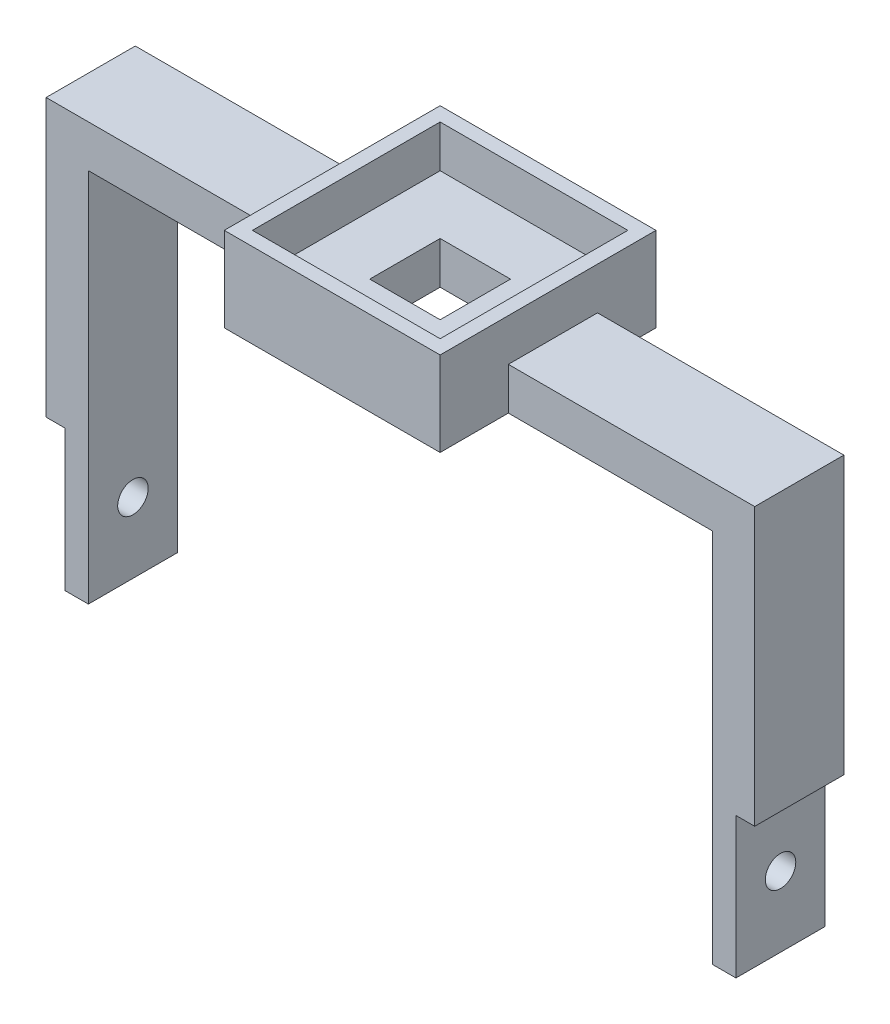
SolidWorks part; units mm, degrees
ref_plane "Ön Düzlem" through (0, 0, 0) normal (0, 0, 1) x (1, 0, 0)
ref_plane "Üst Düzlem" through (0, 0, 0) normal (0, 1, 0) x (1, 0, 0)
ref_plane "Sağ Düzlem" through (0, 0, 0) normal (1, 0, 0) x (0, 0, -1)
sketch "Çizim1" plane through (0, 0, 0) normal (0, 0, 1) x (1, 0, 0)
  line L0 (0, 0) -> (0, 80)
  line L1 (0, 80) -> (133, 80)
  line L2 (133, 80) -> (133, 0)
  line L3 (0, 0) -> (-5, 0)
  line L4 (-5, 0) -> (-5, 30)
  line L5 (142, 89) -> (-9, 89)
  line L6 (-5, 30) -> (-9, 30)
  line L7 (-9, 30) -> (-9, 89)
  line L8 (133, 0) -> (138, 0)
  line L9 (138, 0) -> (138, 30)
  line L10 (138, 30) -> (142, 30)
  line L11 (142, 30) -> (142, 89)
  dimension "D1" = 5
  dimension "D2" = 5
  dimension "D3" = 4
  dimension "D4" = 4
  dimension "D5" = 30
  dimension "D6" = 30
  dimension "D7" = 80
  dimension "D8" = 59
  dimension "D9" = 133
extrude "Yükseklik-Ekstrüzyon1" add sketch "Çizim1" along normal blind 19
sketch "Çizim2" plane through (0, 89, 0) normal (0, 1, 0) x (1, 0, 0)
  line L0 (142, 0) -> (-9, 0) construction
  line L1 (46.5, -30.5382) -> (86.5, -30.5382)
  line L2 (46.5, -30.5382) -> (46.5, 9.4618)
  line L3 (46.5, 9.4618) -> (86.5, 9.4618)
  line L4 (86.5, -30.5382) -> (86.5, 9.4618)
  line L5 (46.5, -30.5382) -> (86.5, 9.4618) construction
  line L6 (46.5, 9.4618) -> (86.5, -30.5382) construction
  point P0 (66.5, -10.5382)
  point P10 (66.5, 0)
  dimension "D1" = 40
  dimension "D2" = 40
  dimension "D3" = 0
extrude "Yükseklik-Ekstrüzyon2" add sketch "Çizim2" against normal up to surface (9 mm away) up to face at (66.5, 80, 9.5)
sketch "Çizim5" plane through (0, 89, 0) normal (0, 1, 0) x (1, 0, 0)
  line L1 (86.5, -30.5382) -> (46.5, -30.5382)
  line L2 (86.5, -30.5382) -> (86.5, 9.4618)
  line L3 (86.5, 9.4618) -> (46.5, 9.4618)
  line L4 (46.5, -30.5382) -> (46.5, 9.4618)
  line L5 (86.5, -30.5382) -> (46.5, 9.4618) construction
  line L6 (86.5, 9.4618) -> (46.5, -30.5382) construction
  line L7 (89.5, -33.5382) -> (43.5, -33.5382)
  line L8 (89.5, -33.5382) -> (89.5, 12.4618)
  line L9 (89.5, 12.4618) -> (43.5, 12.4618)
  line L10 (43.5, -33.5382) -> (43.5, 12.4618)
  line L11 (89.5, -33.5382) -> (43.5, 12.4618) construction
  line L12 (89.5, 12.4618) -> (43.5, -33.5382) construction
  point P0 (66.5, -10.5382)
  point P5 (66.5, -10.5382)
  dimension "D1" = 40
  dimension "D2" = 46
  dimension "D3" = 46
extrude "Yükseklik-Ekstrüzyon3" add sketch "Çizim5" along normal blind 9 and the other way up to surface (9 mm away) other way up to face at (66.5, 80, 9.8461)
sketch "Çizim7" plane through (0, 89, 0) normal (0, 1, 0) x (1, 0, 0)
  line L0 (86.5, 9.4618) -> (46.5, 9.4618) construction
  line L1 (74, -18.0382) -> (59, -18.0382)
  line L2 (74, -18.0382) -> (74, -3.0382)
  line L3 (74, -3.0382) -> (59, -3.0382)
  line L4 (59, -18.0382) -> (59, -3.0382)
  line L5 (74, -18.0382) -> (59, -3.0382) construction
  line L6 (74, -3.0382) -> (59, -18.0382) construction
  line L7 (86.5, -30.5382) -> (86.5, 9.4618) construction
  point P0 (66.5, -10.5382)
  point P7 (66.5, 9.4618)
  point P10 (86.5, -10.5382)
  dimension "D1" = 15
  dimension "D2" = 15
  dimension "D3" = 0
  dimension "D4" = 0
extrude "Kes-Ekstrüzyon1" cut sketch "Çizim7" against normal blind 9 and the other way blind 9
sketch "Çizim8" plane through (138, 0, 0) normal (1, 0, 0) x (0, 0, -1)
  line L0 (-19, 0) -> (0, 0) construction
  circle A0 centre (-9.5, 15) radius 3.25
  dimension "D1" = 6.5
  dimension "D2" = 15
extrude "Kes-Ekstrüzyon2" cut sketch "Çizim8" against normal blind 163
